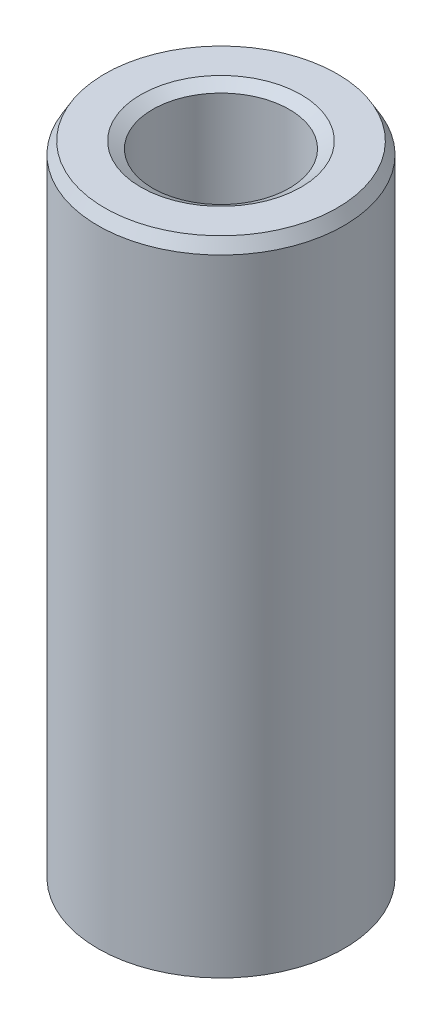
SolidWorks part; units mm, degrees
ref_plane "Front Plane" through (0, 0, 0) normal (0, 0, 1) x (1, 0, 0)
ref_plane "Top Plane" through (0, 0, 0) normal (0, 1, 0) x (1, 0, 0)
ref_plane "Right Plane" through (0, 0, 0) normal (1, 0, 0) x (0, 0, -1)
sketch "Sketch1" plane through (0, 0, 0) normal (0, 1, 0) x (1, 0, 0)
  circle A0 centre (0, 0) radius 7.5
  dimension "SLEEVE_OD" = 15
extrude "Boss-Extrude1" add sketch "Sketch1" along normal blind 39.2923
sketch "Sketch2" plane through (0, 0, 0) normal (0, 1, 0) x (1, 0, 0)
  circle A0 centre (0, 0) radius 4.1633
  dimension "BORE_D" = 8.3267
extrude "Cut-Extrude1" cut sketch "Sketch2" along normal through all
chamfer "Chamfer1" distance 0.723 angle 30 4 edges at (0, 39.2923, 4.1633) (0, 0, 4.1633) (0, 0, 7.5) (0, 39.2923, 7.5) first distance on face at (0, 39.2923, 4.1633) first distance on face at (0, 0, 4.1633) first distance on face at (0, 39.2923, 7.5)
